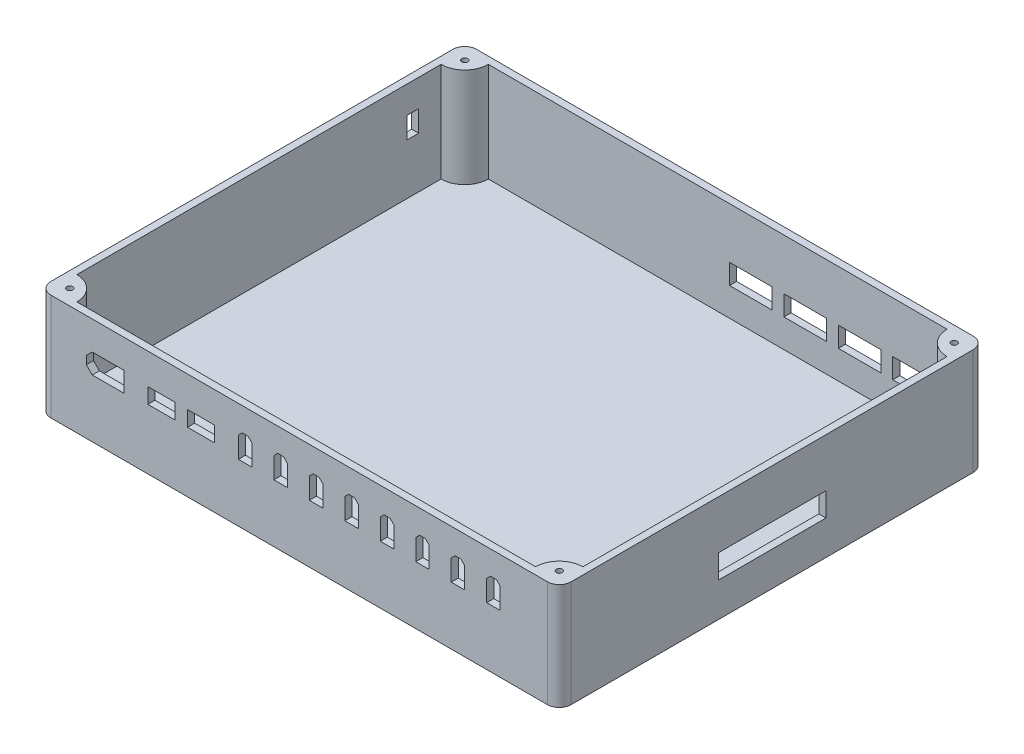
SolidWorks part; units mm, degrees
ref_plane "Front Plane" through (0, 0, 0) normal (0, 0, 1) x (1, 0, 0)
ref_plane "Top Plane" through (0, 0, 0) normal (0, 1, 0) x (1, 0, 0)
ref_plane "Right Plane" through (0, 0, 0) normal (1, 0, 0) x (0, 0, -1)
sketch "Sketch1" plane through (0, 0, 0) normal (0, 1, 0) x (1, 0, 0)
  line L1 (0, 0) -> (220, 0)
  line L2 (0, 0) -> (0, 180)
  line L3 (0, 180) -> (220, 180)
  line L4 (220, 0) -> (220, 180)
  dimension "D1" = 220
  dimension "D2" = 180
extrude "Boss-Extrude1" add sketch "Sketch1" along normal blind 45
fillet "Fillet1" radius 5 4 edges at (0, 22.5, -180) (0, 22.5, 0) (220, 22.5, -180) (220, 22.5, 0)
sketch "Sketch7" plane through (0, 45, 0) normal (0, 1, 0) x (1, 0, 0)
  line L0 (110, 187.4123) -> (110, -2.139) construction
  line L1 (-6.8646, 90) -> (231.1986, 90) construction
  line L2 (207, 177) -> (13, 177)
  line L3 (217, 167) -> (217, 13)
  line L4 (215, 180) -> (5, 180) construction
  line L5 (220, 5) -> (220, 175) construction
  line L6 (207, 3) -> (13, 3)
  line L7 (3, 167) -> (3, 13)
  line L8 (0, 175) -> (0, 5) construction
  line L9 (5, 0) -> (215, 0) construction
  arc A0 (207, 177) -> (217, 167) centre (217, 177) ccw
  arc A1 (207, 3) -> (217, 13) centre (217, 3) cw
  arc A2 (13, 3) -> (3, 13) centre (3, 3) ccw
  arc A3 (13, 177) -> (3, 167) centre (3, 177) cw
  point P14 (217, 90)
  point P18 (110, 3)
  point P23 (110, 177)
  dimension "D5" = 3
  dimension "D1" = 3
  dimension "D2" = 3
  dimension "D3" = 13
  dimension "D4" = 13
  dimension "D6" = 3
extrude "Cut-Extrude7" cut sketch "Sketch7" against normal blind 42
sketch "Sketch2" plane through (0, 0, 0) normal (0, 0, 1) x (1, 0, 0)
  line L0 (175.9, 35) -> (178.4, 35)
  line L1 (190.9, 35) -> (193.4, 35)
  line L2 (189.3, 33.4) -> (189.3, 24.5)
  line L3 (189.3, 24.5) -> (195, 24.5)
  line L4 (195, 33.4) -> (195, 24.5)
  line L5 (174.3, 33.4) -> (174.3, 24.5)
  line L6 (174.3, 24.5) -> (180, 24.5)
  line L7 (180, 33.4) -> (180, 24.5)
  line L8 (160.9, 35) -> (163.4, 35)
  line L9 (159.3, 33.4) -> (159.3, 24.5)
  line L10 (159.3, 24.5) -> (165, 24.5)
  line L11 (165, 33.4) -> (165, 24.5)
  line L12 (145.9, 35) -> (148.4, 35)
  line L13 (144.3, 33.4) -> (144.3, 24.5)
  line L14 (144.3, 24.5) -> (150, 24.5)
  line L15 (150, 33.4) -> (150, 24.5)
  line L16 (130.9, 35) -> (133.4, 35)
  line L17 (129.3, 33.4) -> (129.3, 24.5)
  line L18 (129.3, 24.5) -> (135, 24.5)
  line L19 (135, 33.4) -> (135, 24.5)
  line L20 (115.9, 35) -> (118.4, 35)
  line L21 (114.3, 33.4) -> (114.3, 24.5)
  line L22 (114.3, 24.5) -> (120, 24.5)
  line L23 (120, 33.4) -> (120, 24.5)
  line L24 (100.9, 35) -> (103.4, 35)
  line L25 (99.3, 33.4) -> (99.3, 24.5)
  line L26 (99.3, 24.5) -> (105, 24.5)
  line L27 (105, 33.4) -> (105, 24.5)
  line L28 (85.9, 35) -> (88.4, 35)
  line L29 (84.3, 33.4) -> (84.3, 24.5)
  line L30 (84.3, 24.5) -> (90, 24.5)
  line L31 (90, 33.4) -> (90, 24.5)
  line L33 (215, 0) -> (215, 45) construction
  line L35 (189.3, 33.4) -> (190.9, 35)
  line L36 (193.4, 35) -> (195, 33.4)
  line L37 (178.4, 35) -> (180, 33.4)
  line L38 (174.3, 33.4) -> (175.9, 35)
  line L39 (163.4, 35) -> (165, 33.4)
  line L40 (159.3, 33.4) -> (160.9, 35)
  line L41 (144.3, 33.4) -> (145.9, 35)
  line L42 (148.4, 35) -> (150, 33.4)
  line L43 (133.4, 35) -> (135, 33.4)
  line L44 (129.3, 33.4) -> (130.9, 35)
  line L45 (118.4, 35) -> (120, 33.4)
  line L46 (114.3, 33.4) -> (115.9, 35)
  line L47 (103.4, 35) -> (105, 33.4)
  line L48 (99.3, 33.4) -> (100.9, 35)
  line L49 (88.4, 35) -> (90, 33.4)
  line L50 (84.3, 33.4) -> (85.9, 35)
  point P0 (189.3, 35)
  point P3 (195, 35)
  point P6 (174.3, 35)
  point P9 (180, 35)
  point P10 (159.3, 35)
  point P13 (165, 35)
  point P14 (144.3, 35)
  point P17 (150, 35)
  point P18 (129.3, 35)
  point P21 (135, 35)
  point P22 (114.3, 35)
  point P25 (120, 35)
  point P26 (99.3, 35)
  point P29 (105, 35)
  point P30 (84.3, 35)
  point P33 (90, 35)
  dimension "D1" = 5.7
  dimension "D2" = 10.5
  dimension "D5" = 20
  dimension "D6" = 1.6
  dimension "D7" = 45
  dimension "D8" = 1.6
  dimension "D9" = 45
  dimension "D10" = 1.6
  dimension "D11" = 45
  dimension "D12" = 1.6
  dimension "D13" = 45
  dimension "D14" = 1.6
  dimension "D15" = 45
  dimension "D16" = 1.6
  dimension "D17" = 45
  dimension "D18" = 1.6
  dimension "D19" = 45
  dimension "D20" = 1.6
  dimension "D21" = 45
  dimension "D22" = 1.6
  dimension "D23" = 45
  dimension "D24" = 1.6
  dimension "D25" = 45
  dimension "D26" = 1.6
  dimension "D27" = 45
  dimension "D28" = 1.6
  dimension "D29" = 45
  dimension "D30" = 1.6
  dimension "D31" = 45
  dimension "D32" = 1.6
  dimension "D33" = 45
  dimension "D34" = 1.6
  dimension "D35" = 45
  dimension "D36" = 1.6
  dimension "D37" = 45
sketch "Sketch3" plane through (0, 0, 0) normal (0, 0, 1) x (1, 0, 0)
  line L0 (22.5, 32.9) -> (36, 32.9)
  line L1 (20, 30.4) -> (20, 27)
  line L2 (22.5, 24.5) -> (36, 24.5)
  line L3 (36, 32.9) -> (36, 24.5)
  line L4 (20, 30.4) -> (22.5, 32.9)
  line L5 (20, 27) -> (22.5, 24.5)
  line L6 (5, 0) -> (215, 0) construction
  line L7 (5, 45) -> (5, 0) construction
  point P0 (20, 32.9)
  point P2 (20, 24.5)
  dimension "D1" = 8.4
  dimension "D2" = 16
  dimension "D3" = 16
  dimension "D4" = 2.5
  dimension "D5" = 45
  dimension "D6" = 2.5
  dimension "D7" = 45
  dimension "D8" = 24.5
  dimension "D9" = 15
extrude "Cut-Extrude2" cut sketch "Sketch2" against normal blind 5
extrude "Cut-Extrude3" cut sketch "Sketch3" against normal blind 5
sketch "Sketch4" plane through (0, 0, 0) normal (0, 0, 1) x (1, 0, 0)
  line L0 (5, 0) -> (215, 0) construction
  line L1 (46, 25.5) -> (57.5, 25.5)
  line L2 (46, 25.5) -> (46, 32)
  line L3 (46, 32) -> (57.5, 32)
  line L4 (57.5, 25.5) -> (57.5, 32)
  line L5 (62.8, 25.5) -> (74.3, 25.5)
  line L6 (62.8, 25.5) -> (62.8, 32)
  line L7 (62.8, 32) -> (74.3, 32)
  line L8 (74.3, 25.5) -> (74.3, 32)
  line L9 (50.0473, 25.5) -> (65.0473, 25.5) construction
  line L10 (36, 24.5) -> (36, 32.9) construction
  line L11 (84.3, 33.4) -> (84.3, 24.5) construction
  dimension "D1" = 6.5
  dimension "D2" = 11.5
  dimension "D3" = 25.5
  dimension "D5" = 15
  dimension "D6" = 10
  dimension "D7" = 6.5
  dimension "D8" = 10
  dimension "D4" = 2
extrude "Cut-Extrude4" cut sketch "Sketch4" against normal blind 5
sketch "Sketch5" plane through (220, 0, 0) normal (1, 0, 0) x (0, 0, -1)
  line L0 (175, 0) -> (175, 45) construction
  line L5 (67.2316, 14.4802) -> (112.7684, 14.4802)
  line L7 (67.2316, 14.4802) -> (67.2316, 24.4802)
  line L8 (67.2316, 24.4802) -> (112.7684, 24.4802)
  line L9 (112.7684, 14.4802) -> (112.7684, 24.4802)
  line L10 (5, 45) -> (5, 0) construction
  dimension "D2" = 10
  dimension "D4" = 17.8646
extrude "Cut-Extrude5" cut sketch "Sketch5" against normal blind 5
sketch "Sketch6" plane through (0, 0, -180) normal (0, 0, -1) x (-1, 0, 0)
  line L0 (-215, 45) -> (-215, 0) construction
  line L1 (-202, 23.5) -> (-184, 23.5)
  line L2 (-202, 23.5) -> (-202, 15)
  line L3 (-202, 15) -> (-184, 15)
  line L4 (-184, 23.5) -> (-184, 15)
  line L5 (-215, 0) -> (-5, 0) construction
  line L6 (-179, 23.5) -> (-161, 23.5)
  line L7 (-179, 23.5) -> (-179, 15)
  line L8 (-179, 15) -> (-161, 15)
  line L9 (-161, 23.5) -> (-161, 15)
  line L10 (-156, 23.5) -> (-138, 23.5)
  line L11 (-156, 23.5) -> (-156, 15)
  line L12 (-156, 15) -> (-138, 15)
  line L13 (-138, 23.5) -> (-138, 15)
  line L14 (-133, 23.5) -> (-115, 23.5)
  line L15 (-133, 23.5) -> (-133, 15)
  line L16 (-133, 15) -> (-115, 15)
  line L17 (-115, 23.5) -> (-115, 15)
  line L18 (-202, 23.5) -> (-179, 23.5) construction
  dimension "D1" = 18
  dimension "D2" = 8.5
  dimension "D3" = 13
  dimension "D4" = 15
  dimension "D6" = 23
  dimension "D5" = 4
extrude "Cut-Extrude6" cut sketch "Sketch6" against normal blind 5
sketch "Sketch8" plane through (0, 0, 0) normal (-1, 0, 0) x (0, 0, 1)
  line L0 (-175, 0) -> (-5, 0) construction
  line L1 (-157.5384, 33.5) -> (-152.5384, 33.5)
  line L2 (-157.5384, 33.5) -> (-157.5384, 24.5)
  line L3 (-157.5384, 24.5) -> (-152.5384, 24.5)
  line L4 (-152.5384, 33.5) -> (-152.5384, 24.5)
  dimension "D1" = 9
  dimension "D2" = 5
  dimension "D3" = 24.5
extrude "Cut-Extrude8" cut sketch "Sketch8" against normal blind 4.2
sketch "Sketch10" plane through (0, 45, 0) normal (0, 1, 0) x (1, 0, 0)
  line L0 (110, 184.9025) -> (110, -6.3644) construction
  line L1 (-9.396, 90) -> (224.0695, 90) construction
  line L2 (0, 175) -> (0, 5) construction
  line L3 (110, -4.9025) -> (110, 186.3644) construction
  line L5 (215, 180) -> (5, 180) construction
  circle A0 centre (6.5, 173.5) radius 1.25
  circle A1 centre (213.5, 173.5) radius 1.25
  circle A2 centre (213.5, 6.5) radius 1.25
  circle A3 centre (6.5, 6.5) radius 1.25
  dimension "D1" = 6.5
  dimension "D2" = 6.5
extrude "Cut-Extrude9" cut sketch "Sketch10" against normal blind 40
equation "\"D8@Sketch4\"=\"D6@Sketch4\""
